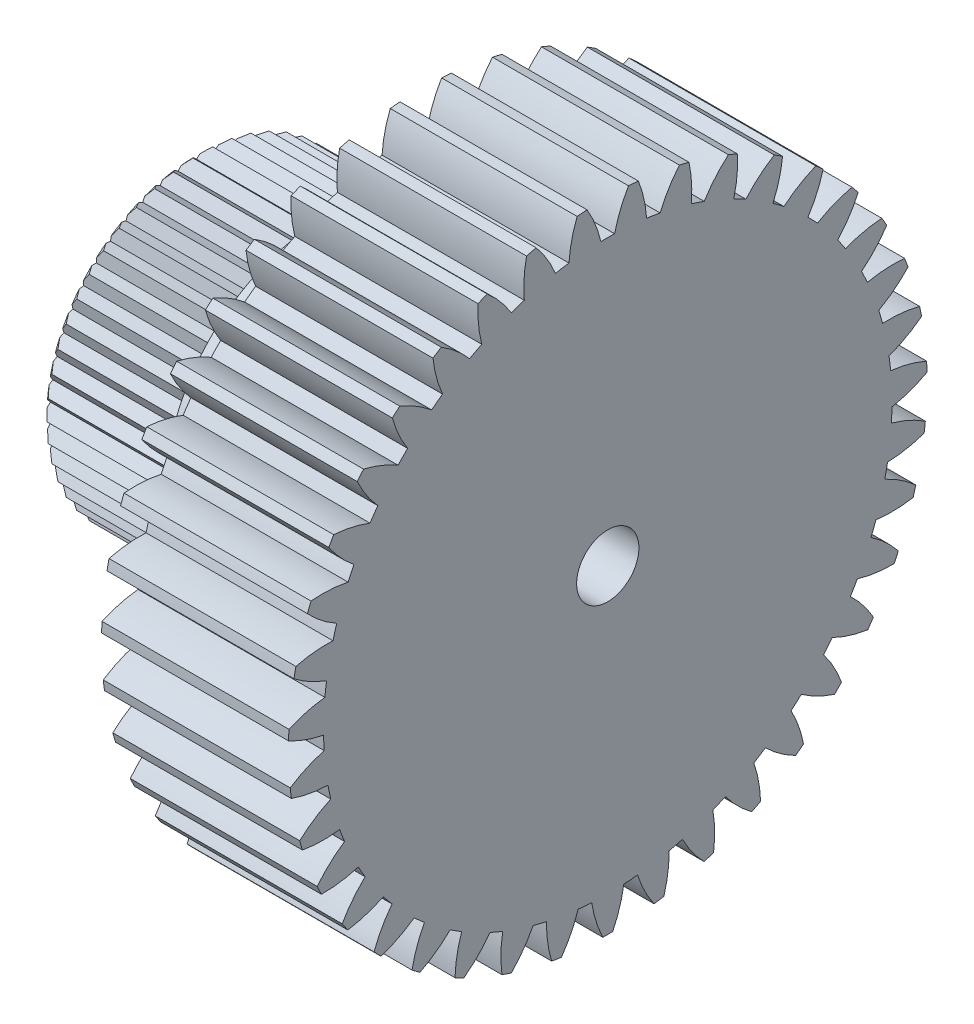
SolidWorks part; units mm, degrees
ref_plane "Plan de face" through (0, 0, 0) normal (0, 0, 1) x (1, 0, 0)
ref_plane "Plan de dessus" through (0, 0, 0) normal (0, 1, 0) x (1, 0, 0)
ref_plane "Plan de droite" through (0, 0, 0) normal (1, 0, 0) x (0, 0, -1)
ref_plane "Plan1" through (0, 0, 0) normal (0, 0, -1) x (-1, 0, 0)
sketch "Esquisse1" plane through (0, 0, 0) normal (0, 0, -1) x (-1, 0, 0)
  line L0 (-3, 5.125) -> (-3, 0)
  line L1 (-3, 0) -> (0, 0)
  line L2 (0, 0) -> (0, 5.125)
  line L3 (0, 5.125) -> (-3, 5.125)
  line L4 (-3, 0) -> (0, 0) construction
revolve "Révolution1" add sketch "Esquisse1" angle 360 about L4 reverse direction yes
sketch "Esquisse2" plane through (3, 0, 0) normal (1, 0, 0) x (0, 0, -1)
  arc A0 (1.9354, 4.7455) -> (1.3036, 4.9564) centre (0, 0) ccw
  arc A1 (1.3036, 4.9564) -> (1.3398, 4.3603) centre (-0.6017, 4.5413) cw
  arc A2 (1.3398, 4.3603) -> (1.5483, 4.2907) centre (0, 0) cw
  arc A3 (1.5483, 4.2907) -> (1.9354, 4.7455) centre (3.2092, 3.269) cw
extrude "Enlèv. mat.-Extru.1" cut sketch "Esquisse2" against normal through all
sketch "Esquisse3" plane through (3, 0, 0) normal (1, 0, 0) x (0, 0, -1)
  arc A0 (2.6716, 4.3736) -> (2.0817, 4.6832) centre (0, 0) ccw
  arc A1 (2.0817, 4.6832) -> (2.0219, 4.0889) centre (0.1345, 4.579) cw
  arc A2 (2.0219, 4.0889) -> (2.2165, 3.9868) centre (0, 0) cw
  arc A3 (2.2165, 3.9868) -> (2.6716, 4.3736) centre (3.692, 2.7119) cw
extrude "Enlèv. mat.-Extru.2" cut sketch "Esquisse3" against normal through all
sketch "Esquisse4" plane through (3, 0, 0) normal (1, 0, 0) x (0, 0, -1)
  arc A0 (3.3386, 3.8884) -> (2.806, 4.2886) centre (0, 0) ccw
  arc A1 (2.806, 4.2886) -> (2.6516, 3.7116) centre (0.8673, 4.4981) cw
  arc A2 (2.6516, 3.7116) -> (2.8273, 3.5796) centre (0, 0) cw
  arc A3 (2.8273, 3.5796) -> (3.3386, 3.8884) centre (4.0793, 2.0845) cw
extrude "Enlèv. mat.-Extru.3" cut sketch "Esquisse4" against normal through all
sketch "Esquisse5" plane through (3, 0, 0) normal (1, 0, 0) x (0, 0, -1)
  arc A0 (3.9191, 3.3025) -> (3.4576, 3.7829) centre (0, 0) ccw
  arc A1 (3.4576, 3.7829) -> (3.2127, 3.2382) centre (1.5776, 4.3008) cw
  arc A2 (3.2127, 3.2382) -> (3.3649, 3.0797) centre (0, 0) cw
  arc A3 (3.3649, 3.0797) -> (3.9191, 3.3025) centre (4.3608, 1.4032) cw
extrude "Enlèv. mat.-Extru.4" cut sketch "Esquisse5" against normal through all
sketch "Esquisse6" plane through (3, 0, 0) normal (1, 0, 0) x (0, 0, -1)
  arc A0 (4.3981, 2.6311) -> (4.0197, 3.1793) centre (0, 0) ccw
  arc A1 (4.0197, 3.1793) -> (3.6905, 2.6809) centre (2.2471, 3.992) cw
  arc A2 (3.6905, 2.6809) -> (3.8154, 2.5) centre (0, 0) cw
  arc A3 (3.8154, 2.5) -> (4.3981, 2.6311) centre (4.5294, 0.6855) cw
extrude "Enlèv. mat.-Extru.5" cut sketch "Esquisse6" against normal through all
sketch "Esquisse7" plane through (3, 0, 0) normal (1, 0, 0) x (0, 0, -1)
  arc A0 (4.7632, 1.8915) -> (4.4776, 2.4933) centre (0, 0) ccw
  arc A1 (4.4776, 2.4933) -> (4.0728, 2.0542) centre (2.8584, 3.5799) cw
  arc A2 (4.0728, 2.0542) -> (4.167, 1.8556) centre (0, 0) cw
  arc A3 (4.167, 1.8556) -> (4.7632, 1.8915) centre (4.5807, -0.05) cw
extrude "Enlèv. mat.-Extru.6" cut sketch "Esquisse7" against normal through all
sketch "Esquisse8" plane through (3, 0, 0) normal (1, 0, 0) x (0, 0, -1)
  arc A0 (5.0049, 1.1029) -> (4.8196, 1.7428) centre (0, 0) ccw
  arc A1 (4.8196, 1.7428) -> (4.3496, 1.3743) centre (3.3956, 3.075) cw
  arc A2 (4.3496, 1.3743) -> (4.4107, 1.1632) centre (0, 0) cw
  arc A3 (4.4107, 1.1632) -> (5.0049, 1.1029) centre (4.5134, -0.7841) cw
extrude "Enlèv. mat.-Extru.7" cut sketch "Esquisse8" against normal through all
sketch "Esquisse9" plane through (3, 0, 0) normal (1, 0, 0) x (0, 0, -1)
  arc A0 (5.117, 0.2858) -> (5.0367, 0.9471) centre (0, 0) ccw
  arc A1 (5.0367, 0.9471) -> (4.5137, 0.6588) centre (3.8449, 2.4905) cw
  arc A2 (4.5137, 0.6588) -> (4.5402, 0.4406) centre (0, 0) cw
  arc A3 (4.5402, 0.4406) -> (5.117, 0.2858) centre (4.3292, -1.498) cw
extrude "Enlèv. mat.-Extru.8" cut sketch "Esquisse9" against normal through all
sketch "Esquisse10" plane through (3, 0, 0) normal (1, 0, 0) x (0, 0, -1)
  arc A0 (5.0966, -0.5387) -> (5.1234, 0.1269) centre (0, 0) ccw
  arc A1 (5.1234, 0.1269) -> (4.5609, -0.0738) centre (4.1946, 1.8415) cw
  arc A2 (4.5609, -0.0738) -> (4.5521, -0.2934) centre (0, 0) cw
  arc A3 (4.5521, -0.2934) -> (5.0966, -0.5387) centre (4.0328, -2.173) cw
extrude "Enlèv. mat.-Extru.9" cut sketch "Esquisse10" against normal through all
sketch "Esquisse11" plane through (3, 0, 0) normal (1, 0, 0) x (0, 0, -1)
  arc A0 (4.9442, -1.3493) -> (5.0774, -0.6966) centre (0, 0) ccw
  arc A1 (5.0774, -0.6966) -> (4.49, -0.8045) centre (4.4357, 1.1448) cw
  arc A2 (4.49, -0.8045) -> (4.446, -1.0198) centre (0, 0) cw
  arc A3 (4.446, -1.0198) -> (4.9442, -1.3493) centre (3.632, -2.7918) cw
extrude "Enlèv. mat.-Extru.10" cut sketch "Esquisse11" against normal through all
sketch "Esquisse12" plane through (3, 0, 0) normal (1, 0, 0) x (0, 0, -1)
  arc A0 (4.6637, -2.1249) -> (4.8999, -1.5021) centre (0, 0) ccw
  arc A1 (4.8999, -1.5021) -> (4.3028, -1.5143) centre (4.5619, 0.4184) cw
  arc A2 (4.3028, -1.5143) -> (4.2249, -1.7198) centre (0, 0) cw
  arc A3 (4.2249, -1.7198) -> (4.6637, -2.1249) centre (3.1371, -3.3382) cw
extrude "Enlèv. mat.-Extru.11" cut sketch "Esquisse12" against normal through all
sketch "Esquisse13" plane through (3, 0, 0) normal (1, 0, 0) x (0, 0, -1)
  arc A0 (4.2625, -2.8455) -> (4.5955, -2.2686) centre (0, 0) ccw
  arc A1 (4.5955, -2.2686) -> (4.0042, -2.1849) centre (4.5699, -0.3188) cw
  arc A2 (4.0042, -2.1849) -> (3.8943, -2.3753) centre (0, 0) cw
  arc A3 (3.8943, -2.3753) -> (4.2625, -2.8455) centre (2.561, -3.7982) cw
extrude "Enlèv. mat.-Extru.12" cut sketch "Esquisse13" against normal through all
sketch "Esquisse14" plane through (3, 0, 0) normal (1, 0, 0) x (0, 0, -1)
  arc A0 (3.7508, -3.4924) -> (4.1721, -2.9764) centre (0, 0) ccw
  arc A1 (4.1721, -2.9764) -> (3.6018, -2.7989) centre (4.4596, -1.0477) cw
  arc A2 (3.6018, -2.7989) -> (3.4628, -2.9692) centre (0, 0) cw
  arc A3 (3.4628, -2.9692) -> (3.7508, -3.4924) centre (1.9186, -4.1599) cw
extrude "Enlèv. mat.-Extru.13" cut sketch "Esquisse14" against normal through all
sketch "Esquisse15" plane through (3, 0, 0) normal (1, 0, 0) x (0, 0, -1)
  arc A0 (3.142, -4.0489) -> (3.6406, -3.6071) centre (0, 0) ccw
  arc A1 (3.6406, -3.6071) -> (3.1062, -3.3405) centre (4.2338, -1.7495) cw
  arc A2 (3.1062, -3.3405) -> (2.9417, -3.4862) centre (0, 0) cw
  arc A3 (2.9417, -3.4862) -> (3.142, -4.0489) centre (1.2264, -4.4138) cw
extrude "Enlèv. mat.-Extru.14" cut sketch "Esquisse15" against normal through all
sketch "Esquisse16" plane through (3, 0, 0) normal (1, 0, 0) x (0, 0, -1)
  arc A0 (2.4518, -4.5005) -> (3.0149, -4.1444) centre (0, 0) ccw
  arc A1 (3.0149, -4.1444) -> (2.5301, -3.7955) centre (3.8983, -2.406) cw
  arc A2 (2.5301, -3.7955) -> (2.3444, -3.9129) centre (0, 0) cw
  arc A3 (2.3444, -3.9129) -> (2.4518, -4.5005) centre (0.5025, -4.5534) cw
extrude "Enlèv. mat.-Extru.15" cut sketch "Esquisse16" against normal through all
sketch "Esquisse17" plane through (3, 0, 0) normal (1, 0, 0) x (0, 0, -1)
  arc A0 (1.6982, -4.8355) -> (2.311, -4.5744) centre (0, 0) ccw
  arc A1 (2.311, -4.5744) -> (1.8885, -4.1522) centre (3.4619, -3.0002) cw
  arc A2 (1.8885, -4.1522) -> (1.6863, -4.2383) centre (0, 0) cw
  arc A3 (1.6863, -4.2383) -> (1.6982, -4.8355) centre (-0.2344, -4.575) cw
extrude "Enlèv. mat.-Extru.16" cut sketch "Esquisse17" against normal through all
sketch "Esquisse18" plane through (3, 0, 0) normal (1, 0, 0) x (0, 0, -1)
  arc A0 (0.9005, -5.0453) -> (1.5473, -4.8858) centre (0, 0) ccw
  arc A1 (1.5473, -4.8858) -> (1.198, -4.4014) centre (2.9358, -3.5167) cw
  arc A2 (1.198, -4.4014) -> (0.9846, -4.454) centre (0, 0) cw
  arc A3 (0.9846, -4.454) -> (0.9005, -5.0453) centre (-0.9652, -4.4782) cw
extrude "Enlèv. mat.-Extru.17" cut sketch "Esquisse18" against normal through all
sketch "Esquisse19" plane through (3, 0, 0) normal (1, 0, 0) x (0, 0, -1)
  arc A0 (0.0795, -5.1244) -> (0.7435, -5.0708) centre (0, 0) ccw
  arc A1 (0.7435, -5.0708) -> (0.4765, -4.5365) centre (2.3336, -3.942) cw
  arc A2 (0.4765, -4.5365) -> (0.2574, -4.5542) centre (0, 0) cw
  arc A3 (0.2574, -4.5542) -> (0.0795, -5.1244) centre (-1.6711, -4.2653) cw
extrude "Enlèv. mat.-Extru.18" cut sketch "Esquisse19" against normal through all
sketch "Esquisse20" plane through (3, 0, 0) normal (1, 0, 0) x (0, 0, -1)
  arc A0 (-0.7435, -5.0708) -> (-0.0795, -5.1244) centre (0, 0) ccw
  arc A1 (-0.0795, -5.1244) -> (-0.2574, -4.5542) centre (1.6711, -4.2653) cw
  arc A2 (-0.2574, -4.5542) -> (-0.4765, -4.5365) centre (0, 0) cw
  arc A3 (-0.4765, -4.5365) -> (-0.7435, -5.0708) centre (-2.3336, -3.942) cw
extrude "Enlèv. mat.-Extru.19" cut sketch "Esquisse20" against normal through all
sketch "Esquisse21" plane through (3, 0, 0) normal (1, 0, 0) x (0, 0, -1)
  arc A0 (-1.5473, -4.8858) -> (-0.9005, -5.0453) centre (0, 0) ccw
  arc A1 (-0.9005, -5.0453) -> (-0.9846, -4.454) centre (0.9652, -4.4782) cw
  arc A2 (-0.9846, -4.454) -> (-1.198, -4.4014) centre (0, 0) cw
  arc A3 (-1.198, -4.4014) -> (-1.5473, -4.8858) centre (-2.9358, -3.5167) cw
extrude "Enlèv. mat.-Extru.20" cut sketch "Esquisse21" against normal through all
sketch "Esquisse22" plane through (3, 0, 0) normal (1, 0, 0) x (0, 0, -1)
  arc A0 (-2.311, -4.5744) -> (-1.6982, -4.8355) centre (0, 0) ccw
  arc A1 (-1.6982, -4.8355) -> (-1.6863, -4.2383) centre (0.2344, -4.575) cw
  arc A2 (-1.6863, -4.2383) -> (-1.8885, -4.1522) centre (0, 0) cw
  arc A3 (-1.8885, -4.1522) -> (-2.311, -4.5744) centre (-3.4619, -3.0002) cw
extrude "Enlèv. mat.-Extru.21" cut sketch "Esquisse22" against normal through all
sketch "Esquisse23" plane through (3, 0, 0) normal (1, 0, 0) x (0, 0, -1)
  arc A0 (-3.0149, -4.1444) -> (-2.4518, -4.5005) centre (0, 0) ccw
  arc A1 (-2.4518, -4.5005) -> (-2.3444, -3.9129) centre (-0.5025, -4.5534) cw
  arc A2 (-2.3444, -3.9129) -> (-2.5301, -3.7955) centre (0, 0) cw
  arc A3 (-2.5301, -3.7955) -> (-3.0149, -4.1444) centre (-3.8983, -2.406) cw
extrude "Enlèv. mat.-Extru.22" cut sketch "Esquisse23" against normal through all
sketch "Esquisse24" plane through (3, 0, 0) normal (1, 0, 0) x (0, 0, -1)
  arc A0 (-3.6406, -3.6071) -> (-3.142, -4.0489) centre (0, 0) ccw
  arc A1 (-3.142, -4.0489) -> (-2.9417, -3.4862) centre (-1.2264, -4.4138) cw
  arc A2 (-2.9417, -3.4862) -> (-3.1062, -3.3405) centre (0, 0) cw
  arc A3 (-3.1062, -3.3405) -> (-3.6406, -3.6071) centre (-4.2338, -1.7495) cw
extrude "Enlèv. mat.-Extru.23" cut sketch "Esquisse24" against normal through all
sketch "Esquisse25" plane through (3, 0, 0) normal (1, 0, 0) x (0, 0, -1)
  arc A0 (-4.1721, -2.9764) -> (-3.7508, -3.4924) centre (0, 0) ccw
  arc A1 (-3.7508, -3.4924) -> (-3.4628, -2.9692) centre (-1.9186, -4.1599) cw
  arc A2 (-3.4628, -2.9692) -> (-3.6018, -2.7989) centre (0, 0) cw
  arc A3 (-3.6018, -2.7989) -> (-4.1721, -2.9764) centre (-4.4596, -1.0477) cw
extrude "Enlèv. mat.-Extru.24" cut sketch "Esquisse25" against normal through all
sketch "Esquisse26" plane through (3, 0, 0) normal (1, 0, 0) x (0, 0, -1)
  arc A0 (-4.5955, -2.2686) -> (-4.2625, -2.8455) centre (0, 0) ccw
  arc A1 (-4.2625, -2.8455) -> (-3.8943, -2.3753) centre (-2.561, -3.7982) cw
  arc A2 (-3.8943, -2.3753) -> (-4.0042, -2.1849) centre (0, 0) cw
  arc A3 (-4.0042, -2.1849) -> (-4.5955, -2.2686) centre (-4.5699, -0.3188) cw
extrude "Enlèv. mat.-Extru.25" cut sketch "Esquisse26" against normal through all
sketch "Esquisse27" plane through (3, 0, 0) normal (1, 0, 0) x (0, 0, -1)
  arc A0 (-4.8999, -1.5021) -> (-4.6637, -2.1249) centre (0, 0) ccw
  arc A1 (-4.6637, -2.1249) -> (-4.2249, -1.7198) centre (-3.1371, -3.3382) cw
  arc A2 (-4.2249, -1.7198) -> (-4.3028, -1.5143) centre (0, 0) cw
  arc A3 (-4.3028, -1.5143) -> (-4.8999, -1.5021) centre (-4.5619, 0.4184) cw
extrude "Enlèv. mat.-Extru.26" cut sketch "Esquisse27" against normal through all
sketch "Esquisse28" plane through (3, 0, 0) normal (1, 0, 0) x (0, 0, -1)
  arc A0 (-5.0774, -0.6966) -> (-4.9442, -1.3493) centre (0, 0) ccw
  arc A1 (-4.9442, -1.3493) -> (-4.446, -1.0198) centre (-3.632, -2.7918) cw
  arc A2 (-4.446, -1.0198) -> (-4.49, -0.8045) centre (0, 0) cw
  arc A3 (-4.49, -0.8045) -> (-5.0774, -0.6966) centre (-4.4357, 1.1448) cw
extrude "Enlèv. mat.-Extru.27" cut sketch "Esquisse28" against normal through all
sketch "Esquisse29" plane through (3, 0, 0) normal (1, 0, 0) x (0, 0, -1)
  arc A0 (-5.1234, 0.1269) -> (-5.0966, -0.5387) centre (0, 0) ccw
  arc A1 (-5.0966, -0.5387) -> (-4.5521, -0.2934) centre (-4.0328, -2.173) cw
  arc A2 (-4.5521, -0.2934) -> (-4.5609, -0.0738) centre (0, 0) cw
  arc A3 (-4.5609, -0.0738) -> (-5.1234, 0.1269) centre (-4.1946, 1.8415) cw
extrude "Enlèv. mat.-Extru.28" cut sketch "Esquisse29" against normal through all
sketch "Esquisse30" plane through (3, 0, 0) normal (1, 0, 0) x (0, 0, -1)
  arc A0 (-5.0367, 0.9471) -> (-5.117, 0.2858) centre (0, 0) ccw
  arc A1 (-5.117, 0.2858) -> (-4.5402, 0.4406) centre (-4.3292, -1.498) cw
  arc A2 (-4.5402, 0.4406) -> (-4.5137, 0.6588) centre (0, 0) cw
  arc A3 (-4.5137, 0.6588) -> (-5.0367, 0.9471) centre (-3.8449, 2.4905) cw
extrude "Enlèv. mat.-Extru.29" cut sketch "Esquisse30" against normal through all
sketch "Esquisse31" plane through (3, 0, 0) normal (1, 0, 0) x (0, 0, -1)
  arc A0 (-4.8196, 1.7428) -> (-5.0049, 1.1029) centre (0, 0) ccw
  arc A1 (-5.0049, 1.1029) -> (-4.4107, 1.1632) centre (-4.5134, -0.7841) cw
  arc A2 (-4.4107, 1.1632) -> (-4.3496, 1.3743) centre (0, 0) cw
  arc A3 (-4.3496, 1.3743) -> (-4.8196, 1.7428) centre (-3.3956, 3.075) cw
extrude "Enlèv. mat.-Extru.30" cut sketch "Esquisse31" against normal through all
sketch "Esquisse32" plane through (3, 0, 0) normal (1, 0, 0) x (0, 0, -1)
  arc A0 (-4.4776, 2.4933) -> (-4.7632, 1.8915) centre (0, 0) ccw
  arc A1 (-4.7632, 1.8915) -> (-4.167, 1.8556) centre (-4.5807, -0.05) cw
  arc A2 (-4.167, 1.8556) -> (-4.0728, 2.0542) centre (0, 0) cw
  arc A3 (-4.0728, 2.0542) -> (-4.4776, 2.4933) centre (-2.8584, 3.5799) cw
extrude "Enlèv. mat.-Extru.31" cut sketch "Esquisse32" against normal through all
sketch "Esquisse33" plane through (3, 0, 0) normal (1, 0, 0) x (0, 0, -1)
  arc A0 (-4.0197, 3.1793) -> (-4.3981, 2.6311) centre (0, 0) ccw
  arc A1 (-4.3981, 2.6311) -> (-3.8154, 2.5) centre (-4.5294, 0.6855) cw
  arc A2 (-3.8154, 2.5) -> (-3.6905, 2.6809) centre (0, 0) cw
  arc A3 (-3.6905, 2.6809) -> (-4.0197, 3.1793) centre (-2.2471, 3.992) cw
extrude "Enlèv. mat.-Extru.32" cut sketch "Esquisse33" against normal through all
sketch "Esquisse34" plane through (3, 0, 0) normal (1, 0, 0) x (0, 0, -1)
  arc A0 (-3.4576, 3.7829) -> (-3.9191, 3.3025) centre (0, 0) ccw
  arc A1 (-3.9191, 3.3025) -> (-3.3649, 3.0797) centre (-4.3608, 1.4032) cw
  arc A2 (-3.3649, 3.0797) -> (-3.2127, 3.2382) centre (0, 0) cw
  arc A3 (-3.2127, 3.2382) -> (-3.4576, 3.7829) centre (-1.5776, 4.3008) cw
extrude "Enlèv. mat.-Extru.33" cut sketch "Esquisse34" against normal through all
sketch "Esquisse35" plane through (3, 0, 0) normal (1, 0, 0) x (0, 0, -1)
  arc A0 (-2.806, 4.2886) -> (-3.3386, 3.8884) centre (0, 0) ccw
  arc A1 (-3.3386, 3.8884) -> (-2.8273, 3.5796) centre (-4.0793, 2.0845) cw
  arc A2 (-2.8273, 3.5796) -> (-2.6516, 3.7116) centre (0, 0) cw
  arc A3 (-2.6516, 3.7116) -> (-2.806, 4.2886) centre (-0.8673, 4.4981) cw
extrude "Enlèv. mat.-Extru.34" cut sketch "Esquisse35" against normal through all
sketch "Esquisse36" plane through (3, 0, 0) normal (1, 0, 0) x (0, 0, -1)
  arc A0 (-2.0817, 4.6832) -> (-2.6716, 4.3736) centre (0, 0) ccw
  arc A1 (-2.6716, 4.3736) -> (-2.2165, 3.9868) centre (-3.692, 2.7119) cw
  arc A2 (-2.2165, 3.9868) -> (-2.0219, 4.0889) centre (0, 0) cw
  arc A3 (-2.0219, 4.0889) -> (-2.0817, 4.6832) centre (-0.1345, 4.579) cw
extrude "Enlèv. mat.-Extru.35" cut sketch "Esquisse36" against normal through all
sketch "Esquisse37" plane through (3, 0, 0) normal (1, 0, 0) x (0, 0, -1)
  arc A0 (-1.3036, 4.9564) -> (-1.9354, 4.7455) centre (0, 0) ccw
  arc A1 (-1.9354, 4.7455) -> (-1.5483, 4.2907) centre (-3.2092, 3.269) cw
  arc A2 (-1.5483, 4.2907) -> (-1.3398, 4.3603) centre (0, 0) cw
  arc A3 (-1.3398, 4.3603) -> (-1.3036, 4.9564) centre (0.6017, 4.5413) cw
extrude "Enlèv. mat.-Extru.36" cut sketch "Esquisse37" against normal through all
sketch "Esquisse38" plane through (3, 0, 0) normal (1, 0, 0) x (0, 0, -1)
  arc A0 (-0.4916, 5.1014) -> (-1.1491, 4.9945) centre (0, 0) ccw
  arc A1 (-1.1491, 4.9945) -> (-0.84, 4.4835) centre (-2.6433, 3.7415) cw
  arc A2 (-0.84, 4.4835) -> (-0.623, 4.5187) centre (0, 0) cw
  arc A3 (-0.623, 4.5187) -> (-0.4916, 5.1014) centre (1.3224, 4.386) cw
extrude "Enlèv. mat.-Extru.37" cut sketch "Esquisse38" against normal through all
sketch "Esquisse39" plane through (3, 0, 0) normal (1, 0, 0) x (0, 0, -1)
  arc A0 (0.3331, 5.1142) -> (-0.3331, 5.1142) centre (0, 0) ccw
  arc A1 (-0.3331, 5.1142) -> (-0.1099, 4.5602) centre (-2.0089, 4.117) cw
  arc A2 (-0.1099, 4.5602) -> (0.1099, 4.5602) centre (0, 0) cw
  arc A3 (0.1099, 4.5602) -> (0.3331, 5.1142) centre (2.0089, 4.117) cw
extrude "Enlèv. mat.-Extru.38" cut sketch "Esquisse39" against normal through all
sketch "Esquisse40" plane through (3, 0, 0) normal (1, 0, 0) x (0, 0, -1)
  arc A0 (1.1491, 4.9945) -> (0.4916, 5.1014) centre (0, 0) ccw
  arc A1 (0.4916, 5.1014) -> (0.623, 4.5187) centre (-1.3224, 4.386) cw
  arc A2 (0.623, 4.5187) -> (0.84, 4.4835) centre (0, 0) cw
  arc A3 (0.84, 4.4835) -> (1.1491, 4.9945) centre (2.6433, 3.7415) cw
extrude "Enlèv. mat.-Extru.39" cut sketch "Esquisse40" against normal through all
hole_wizard "Diamètre du perçage Ø7.0 (7)1" positions "Esquisse42" profile "Esquisse41" hole size "Ø7.0" standard "Ansi Metric"
sketch "Esquisse42" plane through (0, 0, 0) normal (-1, 0, 0) x (0, 0, 1)
  point P0 (0, 0)
sketch "Esquisse41" plane through (0, 0, 0) normal (0, 1, 0) x (0, 0, 1)
  line L0 (0, 0) -> (0, 1)
  line L1 (0, 1) -> (3.5, 1)
  line L2 (3.5, 1) -> (3.5, 0)
  line L5 (3.5, 0) -> (0, 0)
  line L10 (0, 1) -> (-3.5, 1) construction
  line L11 (0, -6.35) -> (0, 107.95) construction
  dimension "Diamètre du perçage" = 7
  dimension "Profondeur du perçage" = 1
  dimension "Angle de pointe" = 180
sketch "Esquisse43" plane through (0, 0, 0) normal (0, 0, 1) x (1, 0, 0)
  line L0 (-3.0001, 2.5) -> (-3.0001, 0)
  line L1 (-3.0001, 0) -> (1, 0)
  line L2 (1, 0) -> (1, 2.5)
  line L3 (1, 2.5) -> (-3.0001, 2.5)
  line L4 (-3.0001, 0) -> (1, 0) construction
revolve "Révolution2" add sketch "Esquisse43" angle 360 about L4 reverse direction yes
hole_wizard "Diamètre du perçage Ø1.0 (1)1" positions "Esquisse45" profile "Esquisse44" hole size "Ø1.0" standard "Ansi Metric"
sketch "Esquisse45" plane through (3, 0, 0) normal (1, 0, 0) x (0, 0, -1)
  point P0 (0, 0)
sketch "Esquisse44" plane through (3, 0, 0) normal (0, 1, 0) x (0, 0, -1)
  line L0 (0, 0) -> (0, 6.0001)
  line L1 (0, 6.0001) -> (0.5, 6.0001)
  line L2 (0.5, 6.0001) -> (0.5, 0)
  line L5 (0.5, 0) -> (0, 0)
  line L11 (0, -6.35) -> (0, 107.95) construction
  dimension "Diamètre du perçage jusqu'au prochain" = 1
  dimension "Profondeur du perçage jusqu'au prochain" = 6.0001
sketch "Esquisse46" plane through (-3.0001, 0, 0) normal (-1, 0, 0) x (0, 0, 1)
  circle A0 centre (0, 0) radius 0.5 construction
  circle A1 centre (0, 0) radius 2.5
  circle A2 centre (0, 0) radius 2.5
  circle A3 centre (0, 0) radius 0.5
  dimension "D1" = 0
extrude "Boss.-Extru.1" add sketch "Esquisse46" along normal blind 0.6
chamfer "Chanfrein1" distance 0.1 angle 45 1 edges at (-3.6001, 0, 2.5)
sketch "Esquisse47" plane through (-3.6001, 0, 0) normal (-1, 0, 0) x (0, 0, 1)
  line L0 (0, 0) -> (0, 3.1941) construction
  line L1 (-0.157, 2.4951) -> (0, 2.35)
  line L2 (0.1955, 3.1082) -> (0, 0) construction
  line L3 (0, 0) -> (-0.186, 2.9567) construction
  line L4 (0, 2.35) -> (0.157, 2.4951)
  line L5 (0.157, 2.4951) -> (0.2945, 2.3315)
  line L6 (0.2945, 2.3315) -> (0.4685, 2.4557)
  line L7 (0.4685, 2.4557) -> (0.5844, 2.2762)
  line L8 (0.5844, 2.2762) -> (0.7725, 2.3776)
  line L9 (0.7725, 2.3776) -> (0.8651, 2.185)
  line L10 (0.8651, 2.185) -> (1.0644, 2.2621)
  line L11 (1.0644, 2.2621) -> (1.1321, 2.0593)
  line L12 (1.1321, 2.0593) -> (1.3396, 2.1108)
  line L13 (1.3396, 2.1108) -> (1.3813, 1.9012)
  line L14 (1.3813, 1.9012) -> (1.5936, 1.9263)
  line L15 (1.5936, 1.9263) -> (1.6087, 1.7131)
  line L16 (1.6087, 1.7131) -> (1.8224, 1.7114)
  line L17 (1.8224, 1.7114) -> (1.8107, 1.4979)
  line L18 (1.8107, 1.4979) -> (2.0225, 1.4695)
  line L19 (2.0225, 1.4695) -> (1.9842, 1.2592)
  line L20 (1.9842, 1.2592) -> (2.1908, 1.2044)
  line L21 (2.1908, 1.2044) -> (2.1263, 1.0006)
  line L22 (2.1263, 1.0006) -> (2.3244, 0.9203)
  line L23 (2.3244, 0.9203) -> (2.235, 0.7262)
  line L24 (2.235, 0.7262) -> (2.4215, 0.6217)
  line L25 (2.4215, 0.6217) -> (2.3084, 0.4403)
  line L26 (2.3084, 0.4403) -> (2.4803, 0.3133)
  line L27 (2.4803, 0.3133) -> (2.3454, 0.1476)
  line L28 (2.3454, 0.1476) -> (2.5, 0)
  line L29 (2.5, 0) -> (2.3454, -0.1476)
  line L30 (2.3454, -0.1476) -> (2.4803, -0.3133)
  line L31 (2.4803, -0.3133) -> (2.3084, -0.4403)
  line L32 (2.3084, -0.4403) -> (2.4215, -0.6217)
  line L33 (2.4215, -0.6217) -> (2.235, -0.7262)
  line L34 (2.235, -0.7262) -> (2.3244, -0.9203)
  line L35 (2.3244, -0.9203) -> (2.1263, -1.0006)
  line L36 (2.1263, -1.0006) -> (2.1908, -1.2044)
  line L37 (2.1908, -1.2044) -> (1.9842, -1.2592)
  line L38 (1.9842, -1.2592) -> (2.0225, -1.4695)
  line L39 (2.0225, -1.4695) -> (1.8107, -1.4979)
  line L40 (1.8107, -1.4979) -> (1.8224, -1.7114)
  line L41 (1.8224, -1.7114) -> (1.6087, -1.7131)
  line L42 (1.6087, -1.7131) -> (1.5936, -1.9263)
  line L43 (1.5936, -1.9263) -> (1.3813, -1.9012)
  line L44 (1.3813, -1.9012) -> (1.3396, -2.1108)
  line L45 (1.3396, -2.1108) -> (1.1321, -2.0593)
  line L46 (1.1321, -2.0593) -> (1.0644, -2.2621)
  line L47 (1.0644, -2.2621) -> (0.8651, -2.185)
  line L48 (0.8651, -2.185) -> (0.7725, -2.3776)
  line L49 (0.7725, -2.3776) -> (0.5844, -2.2762)
  line L50 (0.5844, -2.2762) -> (0.4685, -2.4557)
  line L51 (0.4685, -2.4557) -> (0.2945, -2.3315)
  line L52 (0.2945, -2.3315) -> (0.157, -2.4951)
  line L53 (0.157, -2.4951) -> (0, -2.35)
  line L54 (0, -2.35) -> (-0.157, -2.4951)
  line L55 (-0.157, -2.4951) -> (-0.2945, -2.3315)
  line L56 (-0.2945, -2.3315) -> (-0.4685, -2.4557)
  line L57 (-0.4685, -2.4557) -> (-0.5844, -2.2762)
  line L58 (-0.5844, -2.2762) -> (-0.7725, -2.3776)
  line L59 (-0.7725, -2.3776) -> (-0.8651, -2.185)
  line L60 (-0.8651, -2.185) -> (-1.0644, -2.2621)
  line L61 (-1.0644, -2.2621) -> (-1.1321, -2.0593)
  line L62 (-1.1321, -2.0593) -> (-1.3396, -2.1108)
  line L63 (-1.3396, -2.1108) -> (-1.3813, -1.9012)
  line L64 (-1.3813, -1.9012) -> (-1.5936, -1.9263)
  line L65 (-1.5936, -1.9263) -> (-1.6087, -1.7131)
  line L66 (-1.6087, -1.7131) -> (-1.8224, -1.7114)
  line L67 (-1.8224, -1.7114) -> (-1.8107, -1.4979)
  line L68 (-1.8107, -1.4979) -> (-2.0225, -1.4695)
  line L69 (-2.0225, -1.4695) -> (-1.9842, -1.2592)
  line L70 (-1.9842, -1.2592) -> (-2.1908, -1.2044)
  line L71 (-2.1908, -1.2044) -> (-2.1263, -1.0006)
  line L72 (-2.1263, -1.0006) -> (-2.3244, -0.9203)
  line L73 (-2.3244, -0.9203) -> (-2.235, -0.7262)
  line L74 (-2.235, -0.7262) -> (-2.4215, -0.6217)
  line L75 (-2.4215, -0.6217) -> (-2.3084, -0.4403)
  line L76 (-2.3084, -0.4403) -> (-2.4803, -0.3133)
  line L77 (-2.4803, -0.3133) -> (-2.3454, -0.1476)
  line L78 (-2.3454, -0.1476) -> (-2.5, 0)
  line L79 (-2.5, 0) -> (-2.3454, 0.1476)
  line L80 (-2.3454, 0.1476) -> (-2.4803, 0.3133)
  line L81 (-2.4803, 0.3133) -> (-2.3084, 0.4403)
  line L82 (-2.3084, 0.4403) -> (-2.4215, 0.6217)
  line L83 (-2.4215, 0.6217) -> (-2.235, 0.7262)
  line L84 (-2.235, 0.7262) -> (-2.3244, 0.9203)
  line L85 (-2.3244, 0.9203) -> (-2.1263, 1.0006)
  line L86 (-2.1263, 1.0006) -> (-2.1908, 1.2044)
  line L87 (-2.1908, 1.2044) -> (-1.9842, 1.2592)
  line L88 (-1.9842, 1.2592) -> (-2.0225, 1.4695)
  line L89 (-2.0225, 1.4695) -> (-1.8107, 1.4979)
  line L90 (-1.8107, 1.4979) -> (-1.8224, 1.7114)
  line L91 (-1.8224, 1.7114) -> (-1.6087, 1.7131)
  line L92 (-1.6087, 1.7131) -> (-1.5936, 1.9263)
  line L93 (-1.5936, 1.9263) -> (-1.3813, 1.9012)
  line L94 (-1.3813, 1.9012) -> (-1.3396, 2.1108)
  line L95 (-1.3396, 2.1108) -> (-1.1321, 2.0593)
  line L96 (-1.1321, 2.0593) -> (-1.0644, 2.2621)
  line L97 (-1.0644, 2.2621) -> (-0.8651, 2.185)
  line L98 (-0.8651, 2.185) -> (-0.7725, 2.3776)
  line L99 (-0.7725, 2.3776) -> (-0.5844, 2.2762)
  line L100 (-0.5844, 2.2762) -> (-0.4685, 2.4557)
  line L101 (-0.4685, 2.4557) -> (-0.2945, 2.3315)
  line L102 (-0.2945, 2.3315) -> (-0.157, 2.4951)
  circle A0 centre (0, 0) radius 2.35 construction
  circle A1 centre (0, 0) radius 2.5 construction
  circle A2 centre (0, 0) radius 3.1485
  point P160 (0, 0)
  dimension "D1" = 4.7
  dimension "D4" = 50
  dimension "D2" = 3.6
  dimension "D3" = 3.6
extrude "Enlèv. mat.-Extru.40" cut sketch "Esquisse47" against normal blind 2
